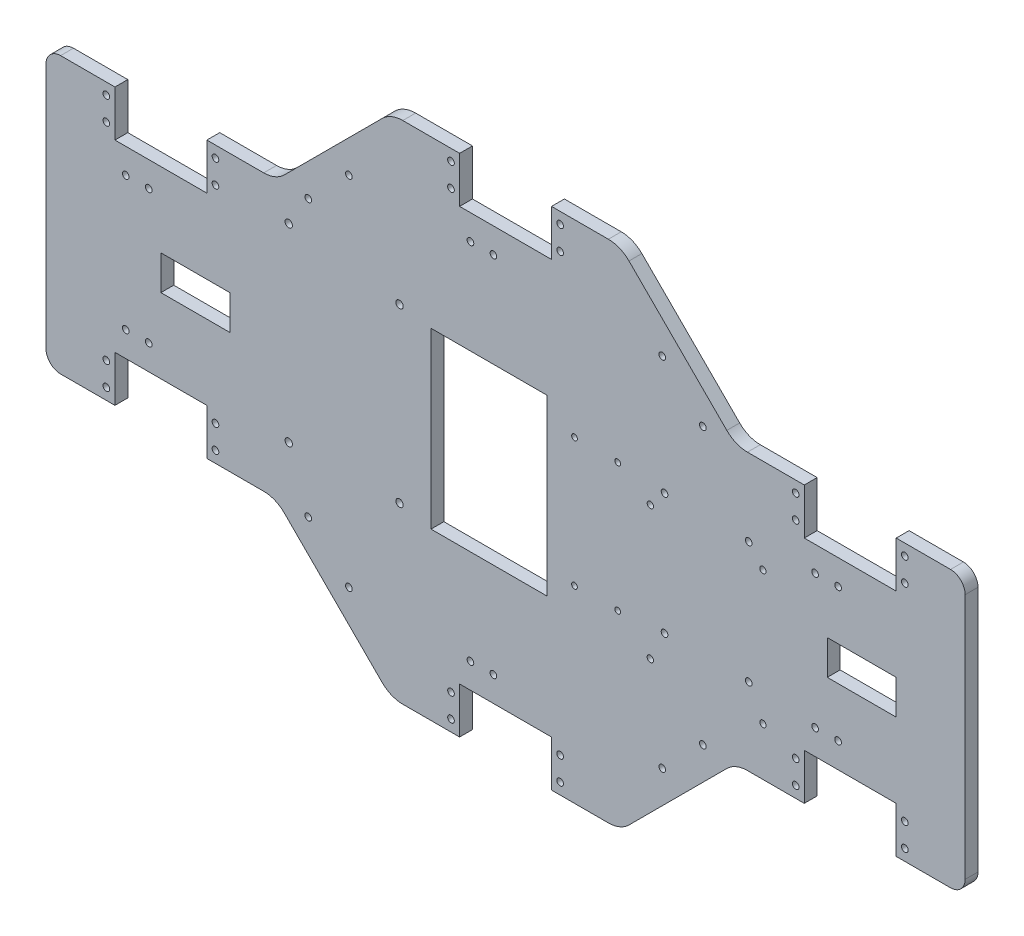
SolidWorks part; units mm, degrees
material "Acrylic (Medium-high impact)"
ref_plane "Front" through (0, 0, 0) normal (0, 0, 1) x (1, 0, 0)
ref_plane "Top" through (0, 0, 0) normal (0, 1, 0) x (1, 0, 0)
ref_plane "Right" through (0, 0, 0) normal (1, 0, 0) x (0, 0, -1)
sketch "Esquisse1" plane through (0, 0, 0) normal (0, 0, 1) x (1, 0, 0)
  line L0 (100, -60) -> (150, -110)
  line L1 (0, 0) -> (25.8386, 0)
  line L2 (0, 0) -> (0, -60)
  line L3 (0, -60) -> (100, -60)
  line L5 (0, 0) -> (100, -60) construction
  line L6 (0, -60) -> (25.8386, 0) construction
  line L7 (150, -110) -> (250, -110)
  line L8 (250, -110) -> (300, -60)
  line L9 (300, -60) -> (400, -60)
  line L10 (400, -60) -> (400, 0)
  line L11 (400, 0) -> (25.8386, 0)
  point P0 (0, 0)
  dimension "D1" = 100
  dimension "D2" = 100
  dimension "D3" = 100
  dimension "D4" = 135
  dimension "D5" = 135
  dimension "D6" = 0
  dimension "D7" = 50
  dimension "D8" = 60
extrude "Boss.-Extru.1" add sketch "Esquisse1" along normal blind 5.6
sketch "Esquisse2" plane through (0, 0, 5.6) normal (0, 0, 1) x (1, 0, 0)
  line L0 (0, -60) -> (100, -60) construction
  line L1 (30, -40) -> (70, -40)
  line L2 (30, -40) -> (30, -60)
  line L3 (30, -60) -> (70, -60)
  line L4 (70, -40) -> (70, -60)
  line L5 (30, -40) -> (70, -60) construction
  line L6 (30, -60) -> (70, -40) construction
  line L7 (0, 0) -> (0, -60) construction
  point P0 (0, -90)
  dimension "D1" = 20
  dimension "D2" = 40
  dimension "D3" = 30
extrude "Enlèv. mat.-Extru.1" cut sketch "Esquisse2" against normal up to next
sketch "Esquisse3" plane through (0, 0, 5.6) normal (0, 0, 1) x (1, 0, 0)
  line L0 (30, -50) -> (70, -50) construction
  line L1 (30, -40) -> (30, -60) construction
  line L2 (70, -60) -> (70, -40) construction
  circle A0 centre (26.25, -55.08) radius 1.45
  circle A1 centre (73.75, -55.08) radius 1.45
  circle A2 centre (73.75, -44.92) radius 1.45
  circle A3 centre (26.25, -44.92) radius 1.45
  circle A4 centre (34.712, -29.09) radius 1.45
  circle A5 centre (44.712, -29.09) radius 1.45
  dimension "D1" = 3.75
  dimension "D2" = 5.08
  dimension "D3" = 47.5
  dimension "D4" = 2.9
  dimension "D5" = 3.75
  dimension "D6" = 2.9
  dimension "D7" = 2.9
  dimension "D8" = 10
  dimension "D9" = 8.462
  dimension "D10" = 15.83
  dimension "D11" = 0
extrude "Enlèv. mat.-Extru.2" cut sketch "Esquisse3" against normal up to next
sketch "Sketch2" plane through (0, 0, 0) normal (0, 0, 1) x (1, 0, 0)
  line L0 (150, -110) -> (250, -110) construction
  line L1 (330, -40) -> (370, -40)
  line L2 (330, -40) -> (330, -60)
  line L3 (330, -60) -> (370, -60)
  line L4 (370, -40) -> (370, -60)
  line L5 (330, -40) -> (370, -60) construction
  line L6 (330, -60) -> (370, -40) construction
  line L7 (300, -60) -> (400, -60) construction
  line L8 (400, -60) -> (400, 0) construction
  line L9 (180, -90) -> (220, -90)
  line L10 (180, -90) -> (180, -110)
  line L11 (180, -110) -> (220, -110)
  line L12 (220, -90) -> (220, -110)
  line L13 (180, -90) -> (220, -110) construction
  line L14 (180, -110) -> (220, -90) construction
  point P0 (0, -90)
  point P11 (-35, 0)
  dimension "D1" = 20
  dimension "D2" = 40
  dimension "D3" = 30
  dimension "D4" = 40
  dimension "D5" = 20
  dimension "D6" = 30
extrude "Cut-Extrude2" cut sketch "Sketch2" against normal through all and the other way through all
sketch "Sketch5" plane through (0, 0, 0) normal (0, 0, 1) x (1, 0, 0)
  line L0 (180, -100) -> (220, -100) construction
  line L1 (220, -110) -> (220, -90) construction
  line L2 (330, -50) -> (370, -50) construction
  line L4 (370, -60) -> (370, -40) construction
  line L5 (330, -40) -> (330, -60) construction
  circle A0 centre (176.25, -105.08) radius 1.45
  circle A1 centre (223.75, -105.08) radius 1.45
  circle A2 centre (223.75, -94.92) radius 1.45
  circle A3 centre (176.25, -94.92) radius 1.45
  circle A4 centre (326.25, -55.08) radius 1.45
  circle A5 centre (373.75, -55.08) radius 1.45
  circle A6 centre (373.75, -44.92) radius 1.45
  circle A7 centre (326.25, -44.92) radius 1.45
  circle A8 centre (184.712, -79.09) radius 1.45
  circle A9 centre (194.712, -79.09) radius 1.45
  circle A10 centre (334.712, -29.09) radius 1.45
  circle A11 centre (344.712, -29.09) radius 1.45
  dimension "D1" = 5.08
  dimension "D2" = 5.08
  dimension "D3" = 47.5
  dimension "D4" = 2.9
  dimension "D5" = 3.75
  dimension "D10" = 2.9
  dimension "D11" = 2.9
  dimension "D12" = 2.9
  dimension "D16" = 2.9
  dimension "D17" = 2.9
  dimension "D6" = 5.08
  dimension "D7" = 5.08
  dimension "D8" = 3.75
  dimension "D9" = 3.75
  dimension "D13" = 10
  dimension "D14" = 8.462
  dimension "D15" = 15.83
  dimension "D18" = 8.462
  dimension "D19" = 15.83
  dimension "D20" = 10
  dimension "D21" = 0
  dimension "D22" = 0
extrude "Cut-Extrude4" cut sketch "Sketch5" along normal through all
mirror "Mirror1" about plane through (0, 0, 0) normal (0, 1, 0) of "Cut-Extrude4", "Cut-Extrude2", "Enlèv. mat.-Extru.1", "Enlèv. mat.-Extru.2", "Boss.-Extru.1"
sketch "Esquisse4" plane through (0, 0, 5.6) normal (0, 0, 1) x (1, 0, 0)
  circle A0 centre (263, -39) radius 1.375
  circle A4 centre (312, -39) radius 1.375
  circle A5 centre (312, 19) radius 1.375
  circle A6 centre (263, 19) radius 1.375
  dimension "D1" = 2.75
  dimension "D2" = 2
  dimension "D3" = 43
  dimension "D4" = 51
  dimension "D5" = 2
extrude "Enlèv. mat.-Extru.4" cut sketch "Esquisse4" against normal through all
sketch "Esquisse6" plane through (0, 0, 0) normal (0, 0, -1) x (-1, 0, 0)
  circle A0 centre (-269.19, -26.31) radius 1.45
  circle A4 centre (-305.82, -26.31) radius 1.45
  circle A5 centre (-305.82, 26.52) radius 1.45
  circle A6 centre (-269.19, 26.52) radius 1.45
  dimension "D1" = 2.9
  dimension "D2" = 2
  dimension "D3" = 63.69
  dimension "D4" = 49.19
  dimension "D5" = 2
extrude "Enlèv. mat.-Extru.6" cut sketch "Esquisse6" against normal through all
sketch "Esquisse8" plane through (0, 0, 0) normal (0, 0, -1) x (-1, 0, 0)
  circle A0 centre (-230, 27.95) radius 1.25
  circle A1 centre (-248.8, 27.95) radius 1.25
  circle A2 centre (-248.8, -27.95) radius 1.25
  circle A3 centre (-230, -27.95) radius 1.25
  dimension "D1" = 2.5
  dimension "D2" = 70
  dimension "D3" = 32.05
  dimension "D4" = 2
  dimension "D5" = 2
extrude "Enlèv. mat.-Extru.7" cut sketch "Esquisse8" against normal through all
sketch "Esquisse9" plane through (0, 0, 0) normal (0, 0, -1) x (-1, 0, 0)
  circle A1 centre (-153.859, -34.88) radius 1.6
  circle A2 centre (-105.639, -36.11) radius 1.6
  circle A3 centre (-105.639, 46.36) radius 1.6
  circle A4 centre (-153.859, 40) radius 1.6
  dimension "D8" = 1.23
  dimension "D1" = 74.88
  dimension "D2" = 82.47
  dimension "D3" = 48.22
  dimension "D4" = 48.22
  dimension "D5" = 48.22
  dimension "D6" = 26.141
  dimension "D7" = 50
extrude "Enlèv. mat.-Extru.8" cut sketch "Esquisse9" against normal through all
sketch "Esquisse10" plane through (0, 0, 0) normal (0, 0, -1) x (-1, 0, 0)
  line L0 (-218, -37.85) -> (-218, 37.84)
  line L1 (-218, 37.84) -> (-167.55, 37.84)
  line L2 (-167.55, 37.84) -> (-167.55, -37.85)
  line L3 (-167.55, -37.85) -> (-218, -37.85)
  dimension "D1" = 50.45
  dimension "D2" = 75.69
  dimension "D3" = 2
  dimension "D4" = 52.16
extrude "Enlèv. mat.-Extru.9" cut sketch "Esquisse10" against normal through all
sketch "Esquisse11" plane through (0, 0, 0) normal (0, 0, -1) x (-1, 0, 0)
  line L1 (-340, 7.5) -> (-370, 7.5)
  line L2 (-340, 7.5) -> (-340, -7.5)
  line L3 (-340, -7.5) -> (-370, -7.5)
  line L4 (-370, 7.5) -> (-370, -7.5)
  line L5 (-50, 7.5) -> (-80, 7.5)
  line L6 (-50, 7.5) -> (-50, -7.5)
  line L7 (-50, -7.5) -> (-80, -7.5)
  line L8 (-80, 7.5) -> (-80, -7.5)
  dimension "D1" = 30
  dimension "D2" = 30
  dimension "D3" = 30
  dimension "D4" = 50
  dimension "D5" = 15
  dimension "D6" = 15
  dimension "D7" = 52.5
  dimension "D8" = 52.5
extrude "Enlèv. mat.-Extru.10" cut sketch "Esquisse11" against normal through all
ref_plane "Plan1" through (200, 0, 0) normal (-1, 0, 0) x (0, 0, 1)
ref_plane "Plan2" through (0, 0, 0) normal (0, 1, 0) x (1, 0, 0)
sketch "Esquisse12" plane through (0, 0, 5.6) normal (0, 0, 1) x (1, 0, 0)
  line L1 (200, 24.0954) -> (200, -24.0954) construction
  line L2 (22.5792, 0) -> (-22.5792, 0) construction
  line L3 (100, 60) -> (150, 110) construction
  circle A0 centre (131.8198, 77.6777) radius 1.45
  circle A1 centre (114.1421, 60) radius 1.45
  circle A2 centre (285.8579, 60) radius 1.45
  circle A3 centre (268.1802, 77.6777) radius 1.45
  circle A4 centre (285.8579, -60) radius 1.45
  circle A5 centre (268.1802, -77.6777) radius 1.45
  circle A6 centre (131.8198, -77.6777) radius 1.45
  circle A7 centre (114.1421, -60) radius 1.45
  dimension "D1" = 2.9
  dimension "D2" = 2.9
  dimension "D3" = 25
  dimension "D4" = 10
  dimension "D5" = 14.1421
  dimension "D6" = 0
extrude "Enlèv. mat.-Extru.11" cut sketch "Esquisse12" against normal through all
fillet "Fillet1" radius 6.35 4 edges at (400, 60, 2.8) (400, -60, 2.8) (0, -60, 2.8) (0, 60, 2.8)
fillet "Fillet2" radius 12.7 8 edges at (150, -110, 2.8) (100, -60, 2.8) (250, -110, 2.8) (300, -60, 2.8) (300, 60, 2.8) (250, 110, 2.8) (150, 110, 2.8) (100, 60, 2.8)
